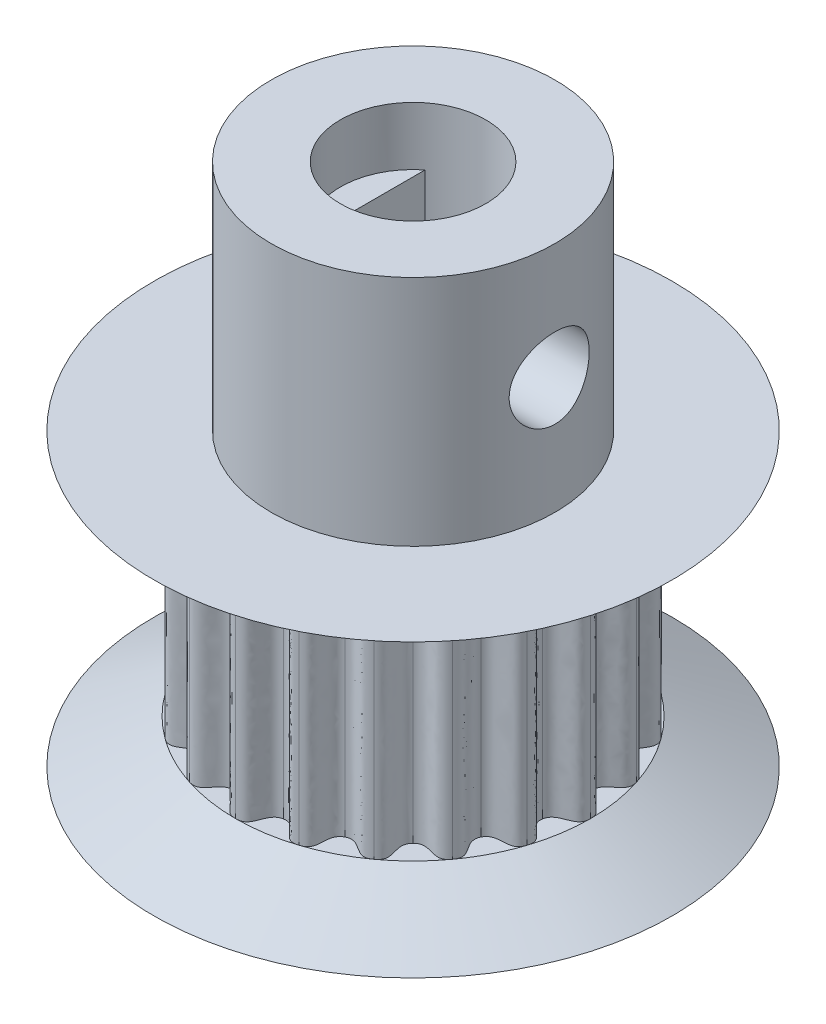
SolidWorks part; units mm, degrees
ref_plane "Front Plane" through (0, 0, 0) normal (0, 0, 1) x (1, 0, 0)
ref_plane "Top Plane" through (0, 0, 0) normal (0, 1, 0) x (1, 0, 0)
ref_plane "Right Plane" through (0, 0, 0) normal (1, 0, 0) x (0, 0, -1)
sketch "Sketch2" plane through (0, 0, 0) normal (0, 1, 0) x (1, 0, 0)
  line L0 (0, 0) -> (0, 6.1) construction
  line L1 (0, 0) -> (-0.9543, 6.0249) construction
  line L2 (0, 0) -> (0.9543, 6.0249) construction
  circle A0 centre (0, 0) radius 6.1 construction
  circle A1 centre (0, 0) radius 5.35 construction
  spline S0 degree 3 poles (0, 6.1) (0.153, 6.1) (0.4902, 5.9418) (0.4716, 5.342) (0.8369, 5.2841) knots 0 0 0 0 0.268003 1 1 1 1
  spline S1 degree 3 poles (0, 6.1) (-0.153, 6.1) (-0.4902, 5.9418) (-0.4716, 5.342) (-0.8369, 5.2841) knots 0 0 0 0 0.268003 1 1 1 1
  spline S2 degree 3 poles (1.885, 5.8014) (1.7395, 5.8487) (1.3699, 5.8025) (1.2022, 5.2263) (0.8369, 5.2841) knots 0 0 0 0 0.268003 1 1 1 1
  spline S3 degree 3 poles (1.885, 5.8014) (2.0305, 5.7542) (2.3024, 5.4995) (2.0993, 4.9348) (2.4288, 4.7669) knots 0 0 0 0 0.268003 1 1 1 1
  spline S4 degree 3 poles (3.5855, 4.935) (3.4617, 5.0249) (3.0959, 5.0952) (2.7584, 4.599) (2.4288, 4.7669) knots 0 0 0 0 0.268003 1 1 1 1
  spline S5 degree 3 poles (3.5855, 4.935) (3.7093, 4.8451) (3.8891, 4.5188) (3.5215, 4.0445) (3.783, 3.783) knots 0 0 0 0 0.268003 1 1 1 1
  spline S6 degree 3 poles (4.935, 3.5855) (4.8451, 3.7093) (4.5188, 3.8891) (4.0445, 3.5215) (3.783, 3.783) knots 0 0 0 0 0.268003 1 1 1 1
  spline S7 degree 3 poles (4.935, 3.5855) (5.0249, 3.4617) (5.0952, 3.0959) (4.599, 2.7584) (4.7669, 2.4288) knots 0 0 0 0 0.268003 1 1 1 1
  spline S8 degree 3 poles (5.8014, 1.885) (5.7542, 2.0305) (5.4995, 2.3024) (4.9348, 2.0993) (4.7669, 2.4288) knots 0 0 0 0 0.268003 1 1 1 1
  spline S9 degree 3 poles (5.8014, 1.885) (5.8487, 1.7395) (5.8025, 1.3699) (5.2263, 1.2022) (5.2841, 0.8369) knots 0 0 0 0 0.268003 1 1 1 1
  spline S10 degree 3 poles (6.1, 0) (6.1, 0.153) (5.9418, 0.4902) (5.342, 0.4716) (5.2841, 0.8369) knots 0 0 0 0 0.268003 1 1 1 1
  spline S11 degree 3 poles (6.1, 0) (6.1, -0.153) (5.9418, -0.4902) (5.342, -0.4716) (5.2841, -0.8369) knots 0 0 0 0 0.268003 1 1 1 1
  spline S12 degree 3 poles (5.8014, -1.885) (5.8487, -1.7395) (5.8025, -1.3699) (5.2263, -1.2022) (5.2841, -0.8369) knots 0 0 0 0 0.268003 1 1 1 1
  spline S13 degree 3 poles (5.8014, -1.885) (5.7542, -2.0305) (5.4995, -2.3024) (4.9348, -2.0993) (4.7669, -2.4288) knots 0 0 0 0 0.268003 1 1 1 1
  spline S14 degree 3 poles (4.935, -3.5855) (5.0249, -3.4617) (5.0952, -3.0959) (4.599, -2.7584) (4.7669, -2.4288) knots 0 0 0 0 0.268003 1 1 1 1
  spline S15 degree 3 poles (4.935, -3.5855) (4.8451, -3.7093) (4.5188, -3.8891) (4.0445, -3.5215) (3.783, -3.783) knots 0 0 0 0 0.268003 1 1 1 1
  spline S16 degree 3 poles (3.5855, -4.935) (3.7093, -4.8451) (3.8891, -4.5188) (3.5215, -4.0445) (3.783, -3.783) knots 0 0 0 0 0.268003 1 1 1 1
  spline S17 degree 3 poles (3.5855, -4.935) (3.4617, -5.0249) (3.0959, -5.0952) (2.7584, -4.599) (2.4288, -4.7669) knots 0 0 0 0 0.268003 1 1 1 1
  spline S18 degree 3 poles (1.885, -5.8014) (2.0305, -5.7542) (2.3024, -5.4995) (2.0993, -4.9348) (2.4288, -4.7669) knots 0 0 0 0 0.268003 1 1 1 1
  spline S19 degree 3 poles (1.885, -5.8014) (1.7395, -5.8487) (1.3699, -5.8025) (1.2022, -5.2263) (0.8369, -5.2841) knots 0 0 0 0 0.268003 1 1 1 1
  spline S20 degree 3 poles (0, -6.1) (0.153, -6.1) (0.4902, -5.9418) (0.4716, -5.342) (0.8369, -5.2841) knots 0 0 0 0 0.268003 1 1 1 1
  spline S21 degree 3 poles (0, -6.1) (-0.153, -6.1) (-0.4902, -5.9418) (-0.4716, -5.342) (-0.8369, -5.2841) knots 0 0 0 0 0.268003 1 1 1 1
  spline S22 degree 3 poles (-1.885, -5.8014) (-1.7395, -5.8487) (-1.3699, -5.8025) (-1.2022, -5.2263) (-0.8369, -5.2841) knots 0 0 0 0 0.268003 1 1 1 1
  spline S23 degree 3 poles (-1.885, -5.8014) (-2.0305, -5.7542) (-2.3024, -5.4995) (-2.0993, -4.9348) (-2.4288, -4.7669) knots 0 0 0 0 0.268003 1 1 1 1
  spline S24 degree 3 poles (-3.5855, -4.935) (-3.4617, -5.0249) (-3.0959, -5.0952) (-2.7584, -4.599) (-2.4288, -4.7669) knots 0 0 0 0 0.268003 1 1 1 1
  spline S25 degree 3 poles (-3.5855, -4.935) (-3.7093, -4.8451) (-3.8891, -4.5188) (-3.5215, -4.0445) (-3.783, -3.783) knots 0 0 0 0 0.268003 1 1 1 1
  spline S26 degree 3 poles (-4.935, -3.5855) (-4.8451, -3.7093) (-4.5188, -3.8891) (-4.0445, -3.5215) (-3.783, -3.783) knots 0 0 0 0 0.268003 1 1 1 1
  spline S27 degree 3 poles (-4.935, -3.5855) (-5.0249, -3.4617) (-5.0952, -3.0959) (-4.599, -2.7584) (-4.7669, -2.4288) knots 0 0 0 0 0.268003 1 1 1 1
  spline S28 degree 3 poles (-5.8014, -1.885) (-5.7542, -2.0305) (-5.4995, -2.3024) (-4.9348, -2.0993) (-4.7669, -2.4288) knots 0 0 0 0 0.268003 1 1 1 1
  spline S29 degree 3 poles (-5.8014, -1.885) (-5.8487, -1.7395) (-5.8025, -1.3699) (-5.2263, -1.2022) (-5.2841, -0.8369) knots 0 0 0 0 0.268003 1 1 1 1
  spline S30 degree 3 poles (-6.1, 0) (-6.1, -0.153) (-5.9418, -0.4902) (-5.342, -0.4716) (-5.2841, -0.8369) knots 0 0 0 0 0.268003 1 1 1 1
  spline S31 degree 3 poles (-6.1, 0) (-6.1, 0.153) (-5.9418, 0.4902) (-5.342, 0.4716) (-5.2841, 0.8369) knots 0 0 0 0 0.268003 1 1 1 1
  spline S32 degree 3 poles (-5.8014, 1.885) (-5.8487, 1.7395) (-5.8025, 1.3699) (-5.2263, 1.2022) (-5.2841, 0.8369) knots 0 0 0 0 0.268003 1 1 1 1
  spline S33 degree 3 poles (-5.8014, 1.885) (-5.7542, 2.0305) (-5.4995, 2.3024) (-4.9348, 2.0993) (-4.7669, 2.4288) knots 0 0 0 0 0.268003 1 1 1 1
  spline S34 degree 3 poles (-4.935, 3.5855) (-5.0249, 3.4617) (-5.0952, 3.0959) (-4.599, 2.7584) (-4.7669, 2.4288) knots 0 0 0 0 0.268003 1 1 1 1
  spline S35 degree 3 poles (-4.935, 3.5855) (-4.8451, 3.7093) (-4.5188, 3.8891) (-4.0445, 3.5215) (-3.783, 3.783) knots 0 0 0 0 0.268003 1 1 1 1
  spline S36 degree 3 poles (-3.5855, 4.935) (-3.7093, 4.8451) (-3.8891, 4.5188) (-3.5215, 4.0445) (-3.783, 3.783) knots 0 0 0 0 0.268003 1 1 1 1
  spline S37 degree 3 poles (-3.5855, 4.935) (-3.4617, 5.0249) (-3.0959, 5.0952) (-2.7584, 4.599) (-2.4288, 4.7669) knots 0 0 0 0 0.268003 1 1 1 1
  spline S38 degree 3 poles (-1.885, 5.8014) (-2.0305, 5.7542) (-2.3024, 5.4995) (-2.0993, 4.9348) (-2.4288, 4.7669) knots 0 0 0 0 0.268003 1 1 1 1
  spline S39 degree 3 poles (-1.885, 5.8014) (-1.7395, 5.8487) (-1.3699, 5.8025) (-1.2022, 5.2263) (-0.8369, 5.2841) knots 0 0 0 0 0.268003 1 1 1 1
  point P148 (0, 0)
  dimension "D1" = 12.2
  dimension "D3" = 0.75
  dimension "D2" = 9
extrude "Boss-Extrude3" add sketch "Sketch2" along normal mid plane 7
sketch "Sketch3" plane through (0, -3.5, 0) normal (0, -1, 0) x (1, 0, 0)
  circle A0 centre (0, 0) radius 6.1
ref_plane "Plane1" through (0, -5, 0) normal (0, -1, 0) x (-1, 0, 0)
sketch "Sketch4" plane through (0, -5, 0) normal (0, -1, 0) x (-1, 0, 0)
  circle A0 centre (0, 0) radius 8.9
  dimension "D1" = 17.8
loft "Loft1" add profiles "Sketch4", "Sketch3" connector at (8.6619, -5, -2.045) connector at (5.9572, -3.5, -1.312)
mirror "Mirror1" about plane through (0, 0, 0) normal (0, 1, 0) of bodies 104
combine bodies "Combine1" operation type add bodies to combine 104 103 105
sketch "Sketch5" plane through (0, 5, 0) normal (0, 1, 0) x (1, 0, 0)
  line L0 (0, 2.5) -> (0, -2.5) construction
  line L1 (1.55, 1.9615) -> (1.55, -1.9615)
  line L2 (-1.55, 1.9615) -> (-1.55, -1.9615)
  circle A0 centre (0, 0) radius 2.5
  circle A1 centre (0, 0) radius 4.875
  dimension "D1" = 5
  dimension "D2" = 9.75
  dimension "D3" = 3.1
extrude "Boss-Extrude4" add sketch "Sketch5" along normal blind 8 contours A1 A0 | L2 A0 | L1 A0 region at (1.937, 5, 0) region at (-1.937, 5, 0) region at (-4.7371, 5, 0)
sketch "Sketch6" plane through (-1.55, 0, 0) normal (1, 0, 0) x (0, 0, -1)
  line L0 (0, 5) -> (0, 13) construction
  line L1 (8.9, 5) -> (-8.9, 5) construction
  line L2 (4.875, 13) -> (-4.875, 13) construction
  circle A0 centre (0, 9) radius 1.375
  dimension "D1" = 2.75
extrude "Cut-Extrude1" cut sketch "Sketch6" along normal up to surface (6.2271 mm away) up to face at (0, 13, 4.875)
sketch "Sketch7" plane through (0, 13, 0) normal (0, 1, 0) x (1, 0, 0)
  circle A0 centre (0, 0) radius 2.5
  arc A1 (1.55, 1.9615) -> (-1.55, 1.9615) centre (0, 0) ccw construction
extrude "Cut-Extrude2" cut sketch "Sketch7" against normal blind 2
